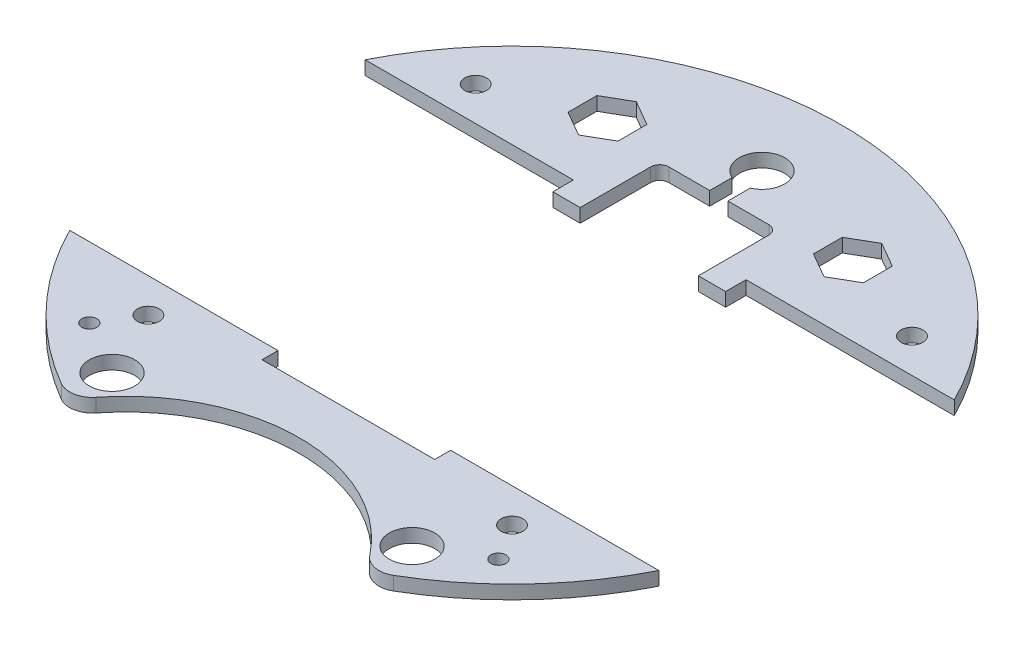
SolidWorks part; units mm, degrees
material "Acrylic (Medium-high impact)"
ref_plane "Front Plane" through (0, 0, 0) normal (0, 0, 1) x (1, 0, 0)
ref_plane "Top Plane" through (0, 0, 0) normal (0, 1, 0) x (1, 0, 0)
ref_plane "Right Plane" through (0, 0, 0) normal (1, 0, 0) x (0, 0, -1)
sketch "Sketch1" plane through (0, 0, 0) normal (0, 1, 0) x (1, 0, 0)
  line L0 (0, -85) -> (-32.4891, -64.8129) construction
  line L1 (0, -85) -> (0, 0) construction
  arc A0 (36.5434, -62.6165) -> (-36.5434, -62.6165) centre (0, 0) ccw
  arc A1 (30.0898, -61.3851) -> (-30.0898, -61.3851) centre (0, -85) ccw
  arc A2 (36.5434, -62.6165) -> (30.0898, -61.3851) centre (34.0231, -58.2982) cw
  arc A3 (-30.0898, -61.3851) -> (-36.5434, -62.6165) centre (-34.0231, -58.2982) cw
  dimension "D1" = 145
  dimension "D2" = 76.5
  dimension "D4" = 5
  dimension "D3" = 85
extrude "Boss-Extrude1" add sketch "Sketch1" along normal blind 3
sketch "solenoid placement" plane through (0, 3, 0) normal (0, 1, 0) x (1, 0, 0)
  line L4 (-19, -36) -> (19, -36)
  line L5 (-19, 28) -> (-19, -36)
  line L6 (19, 28) -> (-19, 28)
  line L7 (19, -36) -> (19, 28)
  line L8 (-19, -36) -> (19, -36)
  line L9 (-19, 28) -> (-19, -36)
  line L10 (19, 28) -> (-19, 28)
  line L11 (19, -36) -> (19, 28)
  dimension "D1" = 0
extrude "Cut-Extrude1" cut sketch "solenoid placement" against normal through all
sketch "Sketch5" plane through (0, 3, 0) normal (0, 1, 0) x (1, 0, 0)
  line L12 (-21.5, 51.1754) -> (-27, 54.3509)
  line L13 (-27, 54.3509) -> (-32.5, 51.1754)
  line L14 (-32.5, 51.1754) -> (-32.5, 44.8246)
  line L15 (-32.5, 44.8246) -> (-27, 41.6491)
  line L16 (-27, 41.6491) -> (-21.5, 44.8246)
  line L17 (-21.5, 44.8246) -> (-21.5, 51.1754)
  line L18 (-21.5, 51.1754) -> (-27, 54.3509)
  line L19 (-27, 54.3509) -> (-32.5, 51.1754)
  line L20 (-32.5, 51.1754) -> (-32.5, 44.8246)
  line L21 (-32.5, 44.8246) -> (-27, 41.6491)
  line L22 (-27, 41.6491) -> (-21.5, 44.8246)
  line L23 (-21.5, 44.8246) -> (-21.5, 51.1754)
  line L24 (21.5, 51.1754) -> (21.5, 44.8246)
  line L25 (21.5, 44.8246) -> (27, 41.6491)
  line L26 (27, 41.6491) -> (32.5, 44.8246)
  line L27 (32.5, 44.8246) -> (32.5, 51.1754)
  line L28 (32.5, 51.1754) -> (27, 54.3509)
  line L29 (27, 54.3509) -> (21.5, 51.1754)
  line L42 (21.5, 51.1754) -> (21.5, 44.8246)
  line L43 (21.5, 44.8246) -> (27, 41.6491)
  line L44 (27, 41.6491) -> (32.5, 44.8246)
  line L45 (32.5, 44.8246) -> (32.5, 51.1754)
  line L46 (32.5, 51.1754) -> (27, 54.3509)
  line L47 (27, 54.3509) -> (21.5, 51.1754)
  dimension "D1" = 0
  dimension "D2" = 0
extrude "Cut-Extrude5" cut sketch "Sketch5" against normal through all
sketch "Sketch6" plane through (0, 3, 0) normal (0, 1, 0) x (1, 0, 0)
  circle A0 centre (48, 40) radius 2.4
  circle A1 centre (40, -40) radius 2.4
  circle A2 centre (40, -40) radius 2.4 construction
  circle A3 centre (-40, -40) radius 2.4
  circle A4 centre (-40, -40) radius 2.4 construction
  circle A5 centre (48, 40) radius 2.4
  circle A6 centre (48, 40) radius 2.4 construction
  circle A7 centre (-48, 40) radius 2.4
  circle A8 centre (-48, 40) radius 2.4 construction
  circle A9 centre (-48, 40) radius 2.4
  circle A10 centre (40, -40) radius 2.4
  circle A11 centre (-40, -40) radius 2.4
  dimension "D5" = 4.8
extrude "Cut-Extrude6" cut sketch "Sketch6" against normal through all
sketch "Sketch3" plane through (0, 3, 0) normal (0, 1, 0) x (1, 0, 0)
  line L0 (-19, 28) -> (-19, 32.5)
  line L1 (72.5, -32.5) -> (-72.5, -32.5)
  line L2 (72.5, -32.5) -> (72.5, 32.5)
  line L3 (72.5, 32.5) -> (19, 32.5)
  line L4 (-72.5, -32.5) -> (-72.5, 32.5)
  line L5 (72.5, -32.5) -> (-72.5, 32.5) construction
  line L6 (72.5, 32.5) -> (-72.5, -32.5) construction
  line L7 (-19, 28) -> (19, 28)
  line L8 (19, 28) -> (19, 32.5)
  line L9 (-19, 32.5) -> (-72.5, 32.5)
  line L10 (-19, 28) -> (-19, -36) construction
  arc A0 (36.5434, -62.6165) -> (-36.5434, -62.6165) centre (0, 0) ccw construction
  point P0 (0, 0)
  dimension "D1" = 65
extrude "Cut-Extrude3" cut sketch "Sketch3" against normal through all
sketch "Sketch7" plane through (0, 3, 0) normal (0, 1, 0) x (1, 0, 0)
  line L8 (13, 28) -> (13, 43.5)
  line L9 (-13, 28) -> (13, 28)
  line L10 (-13, 43.5) -> (-13, 28)
  line L11 (11, 45.5) -> (-11, 45.5)
  line L28 (13, 28) -> (13, 43.5)
  line L29 (-13, 28) -> (13, 28)
  line L30 (-13, 43.5) -> (-13, 28)
  line L31 (11, 45.5) -> (-11, 45.5)
  arc A4 (-11, 45.5) -> (-13, 43.5) centre (-11, 43.5) ccw
  arc A5 (13, 43.5) -> (11, 45.5) centre (11, 43.5) ccw
  arc A14 (-11, 45.5) -> (-13, 43.5) centre (-11, 43.5) ccw
  arc A15 (13, 43.5) -> (11, 45.5) centre (11, 43.5) ccw
  dimension "D1" = 0
extrude "Cut-Extrude7" cut sketch "Sketch7" against normal through all
sketch "Sketch8" plane through (0, 3, 0) normal (0, 1, 0) x (1, 0, 0)
  line L0 (0, 0) -> (0, -21.9152) construction
  circle A1 centre (33, -55) radius 5
  circle A4 centre (-33, -55) radius 5
  dimension "D3" = 10
  dimension "D1" = 33
  dimension "D2" = 55
extrude "Cut-Extrude8" cut sketch "Sketch8" against normal through all
sketch "Sketch9" plane through (0, 3, 0) normal (0, 1, 0) x (1, 0, 0)
  line L0 (0, 0) -> (0, 55) construction
  line L1 (2, 0) -> (2, 50.4174)
  line L2 (-2, 0) -> (-2, 50.4174)
  line L3 (2, 0) -> (2, 55) construction
  line L4 (-2, 0) -> (-2, 55) construction
  arc A0 (2, 50.4174) -> (-2, 50.4174) centre (0, 55) ccw
  arc A1 (2, 0) -> (-2, 0) centre (0, 0) cw
  dimension "D1" = 10
  dimension "D2" = 55
  dimension "D3" = 2
  dimension "D4" = 2
extrude "Cut-Extrude9" cut sketch "Sketch9" against normal through all
sketch "Sketch10" plane through (0, 3, 0) normal (0, 1, 0) x (1, 0, 0)
  line L0 (0, 0) -> (0, -25.927) construction
  circle A0 centre (45, -48) radius 1.65
  circle A1 centre (-45, -48) radius 1.65
  dimension "D3" = 3.3
  dimension "D1" = 45
  dimension "D2" = 48
extrude "Cut-Extrude10" cut sketch "Sketch10" against normal blind 10
equation "\"smallPulleyTeeth\"= 30"
equation "\"largePulleyTeeth\"= 30"
equation "\"eighthThick\"= 3.0mm"
equation "\"sixteenthThick\" = 1.7mm"
equation "\"quarterThick\"=6.0mm"
equation "\"OD\" = 145mm"
equation "\"puckAngle\" = 60.5deg"
equation "\"D1@Sketch1\"=\"OD\""
equation "\"puckDiam\" = 76.5mm"
equation "\"D2@Sketch1\"=\"puckDiam\""
equation "\"D1@Boss-Extrude1\"=\"eighthThick\""
equation "\"axlePress\" = 5.9mm"
equation "\"press\" = 0.2mm"
equation "\"wheelClear\" = 0.3mm"
equation "\"10-32clear\" = 4.8mm"
equation "\"6-32clear\" = 3.3mm"
equation "\"8-32clear\" = 4.0mm"
equation "\"wheelHeight\" = 22mm"
equation "\"wheelWell\" = 65mm"
equation "\"D1@Sketch3\"=\"wheelWell\""
equation "\"puckDist\" = 85mm"
equation "\"scoopFillet\" = 5mm"
equation "\"4-40clear\" = 3.0mm"
equation "\"D3@Sketch1\"=\"puckDist\""
equation "\"D4@Sketch1\"=\"scoopFillet\""
equation "\"10-32tap\" = 4.45mm"
equation "\"D5@Sketch6\"=\"10-32clear\""
equation "\"D3@Sketch10\"=\"6-32clear\""
